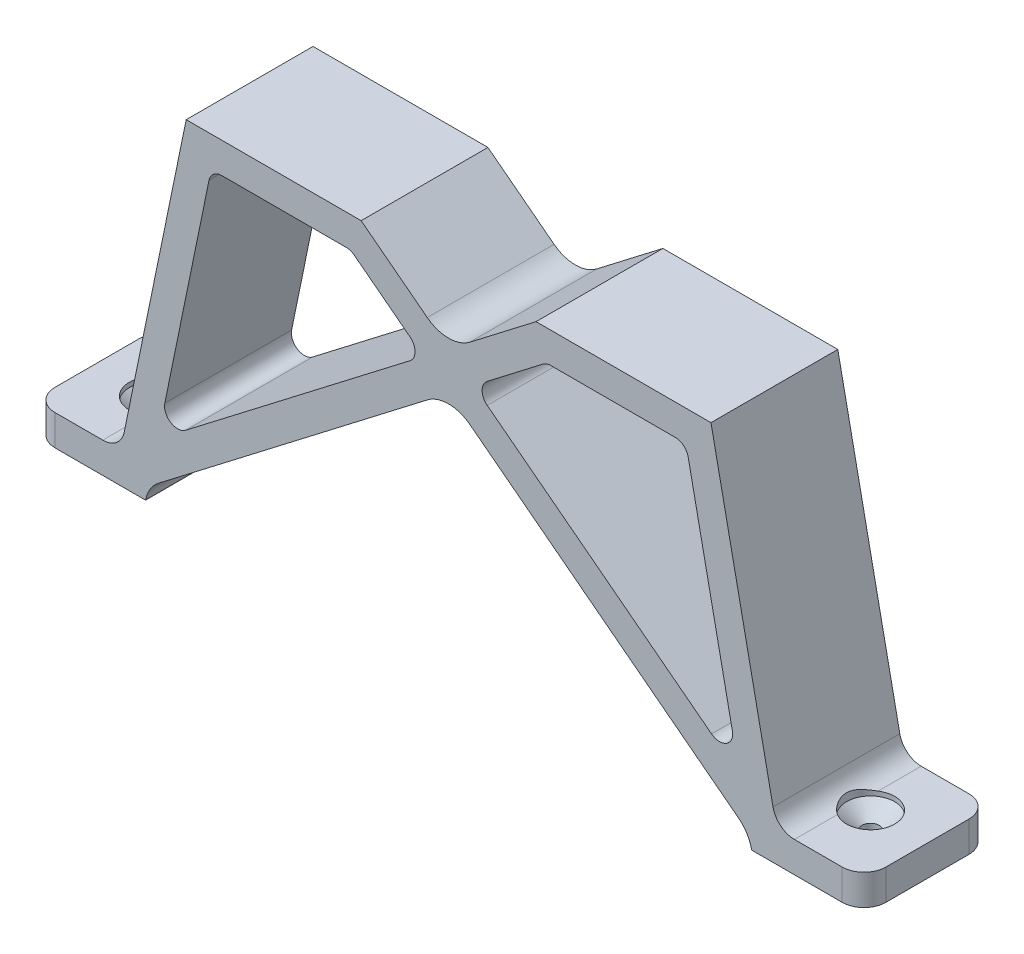
SolidWorks part; units mm, degrees
material "ABS"
ref_plane "Front" through (0, 0, 0) normal (0, 0, 1) x (1, 0, 0)
ref_plane "Top" through (0, 0, 0) normal (0, 1, 0) x (1, 0, 0)
ref_plane "Right" through (0, 0, 0) normal (1, 0, 0) x (0, 0, -1)
sketch "Esquisse1" plane through (0, 0, 0) normal (0, 0, 1) x (1, 0, 0)
  line L0 (-95, 0) -> (-75, 0)
  line L1 (-75, 0) -> (-60, 73)
  line L2 (-60, 73) -> (-20, 73)
  line L3 (0, 73) -> (0, 0) construction
  line L4 (-75, 0) -> (75, 0) construction
  line L6 (-20, 73) -> (75, 0)
  dimension "D1" = 73
  dimension "D2" = 15
  dimension "D3" = 20
  dimension "D4" = 120
  dimension "D5" = 40
extrude "Extru.-Mince1" add sketch "Esquisse1" along normal mid plane 29 thin thin type one direction wall 7
fillet "Congé1" radius 5 2 edges at (-95, -3.5, -14.5) (-95, -3.5, 14.5)
fillet "Congé2" radius 5 1 edges at (-75, 0, 0)
sketch "Esquisse4" plane through (0, -7, 0) normal (0, -1, 0) x (1, 0, 0)
  line L0 (-60, 14.5) -> (-60, -14.5) construction
  circle A0 centre (-82, 0) radius 2
  point P2 (0, 0)
  dimension "D1" = 4
  dimension "D2" = 22
extrude "Enlèv. mat.-Extru.1" cut sketch "Esquisse4" against normal blind 3
sketch "Esquisse5" plane through (0, -4, 0) normal (0, -1, 0) x (1, 0, 0)
  circle A0 centre (-82, 0) radius 5.5
  dimension "D1" = 11
extrude "Enlèv. mat.-Extru.2" cut sketch "Esquisse5" against normal through all
chamfer "Chanfrein1" distance 3.5 angle 40 1 edges at (-76.5, -4, 0) first distance on face at (-80, -4, 0)
mirror "Symétrie1" about plane through (0, 0, 0) normal (1, 0, 0) of bodies 104
fillet "Congé3" radius 8 4 edges at (0, 57.6316, 0) (0, 48.8036, 0) (68.6679, -3.9623, 0) (-68.6679, -3.9623, 0)
fillet "Congé4" radius 3 8 edges at (54.2921, 66, 0) (5.7442, 53.2176, 0) (66.5138, 6.521, 0) (22.3789, 66, 0) (-22.3789, 66, 0) (-66.5138, 6.521, 0) (-5.7442, 53.2176, 0) (-54.2921, 66, 0)
